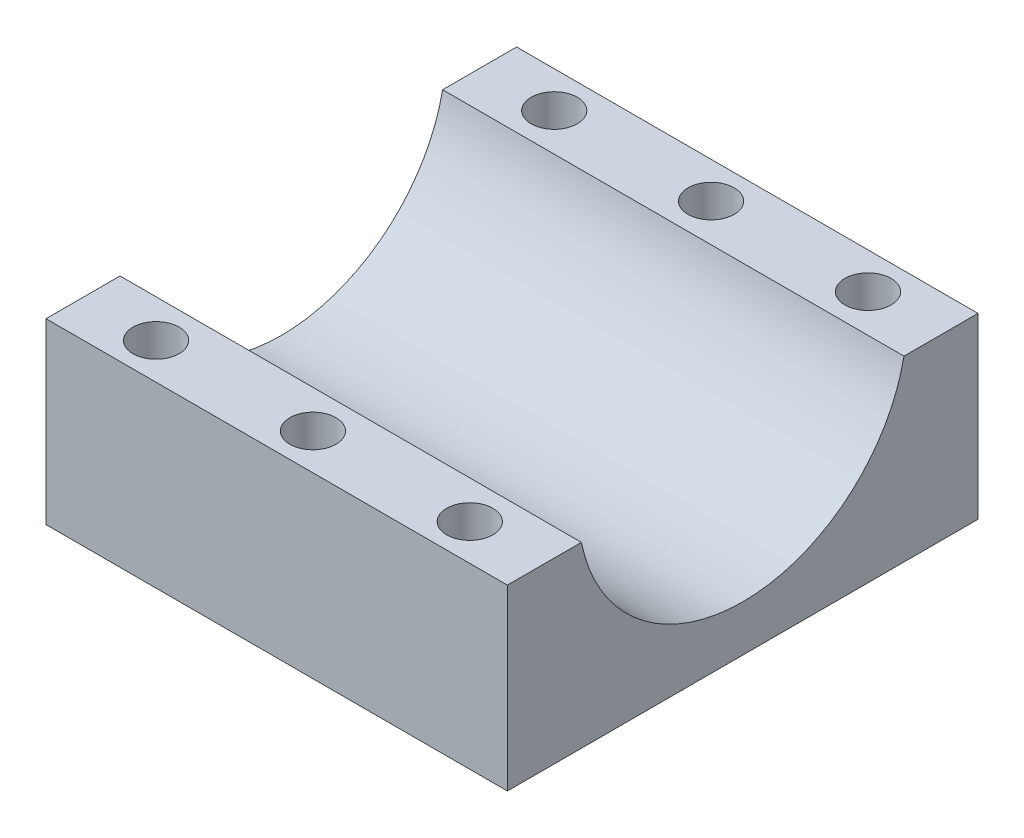
SolidWorks part; units mm, degrees
ref_plane "Front Plane" through (0, 0, 0) normal (0, 0, 1) x (1, 0, 0)
ref_plane "Top Plane" through (0, 0, 0) normal (0, 1, 0) x (1, 0, 0)
ref_plane "Right Plane" through (0, 0, 0) normal (1, 0, 0) x (0, 0, -1)
sketch "Sketch1" plane through (0, 0, 0) normal (0, 1, 0) x (1, 0, 0)
  line L0 (-40.0608, 0) -> (47.511, 0) construction
  line L1 (-25, -25.5) -> (25, -25.5)
  line L2 (-25, -25.5) -> (-25, 25.5)
  line L3 (-25, 25.5) -> (25, 25.5)
  line L4 (25, -25.5) -> (25, 25.5)
  line L5 (-25, -25.5) -> (25, 25.5) construction
  line L6 (-25, 25.5) -> (25, -25.5) construction
  line L7 (-25, 21.575) -> (25, 21.575) construction
  line L8 (-25, 18.075) -> (25, 18.075) construction
  line L9 (-25, -21.575) -> (25, -21.575) construction
  line L10 (-25, -18.075) -> (25, -18.075) construction
  line L11 (0, -25.5) -> (0, 25.5) construction
  circle A0 centre (-17, 21.575) radius 2.5
  circle A1 centre (17, 21.575) radius 2.5
  circle A2 centre (17, -21.575) radius 2.5
  circle A3 centre (-17, -21.575) radius 2.5
  circle A4 centre (0, 21.575) radius 2.5
  circle A5 centre (0, -21.575) radius 2.5
  point P0 (0, 0)
  dimension "D3" = 5
  dimension "D4" = 5
  dimension "D9" = 5
  dimension "D10" = 5
  dimension "D1" = 50
  dimension "D2" = 51
  dimension "D5" = 8
  dimension "D6" = 8
  dimension "D7" = 18.075
  dimension "D8" = 3.5
extrude "Boss-Extrude1" add sketch "Sketch1" along normal blind 19.325
sketch "Sketch2" plane through (25, 0, 0) normal (1, 0, 0) x (0, 0, -1)
  line L0 (-25.5, 19.325) -> (25.5, 19.325) construction
  circle A0 centre (0, 22.825) radius 17.825
  dimension "D2" = 35.65
  dimension "D1" = 3.5
extrude "Cut-Extrude1" cut sketch "Sketch2" against normal through all
